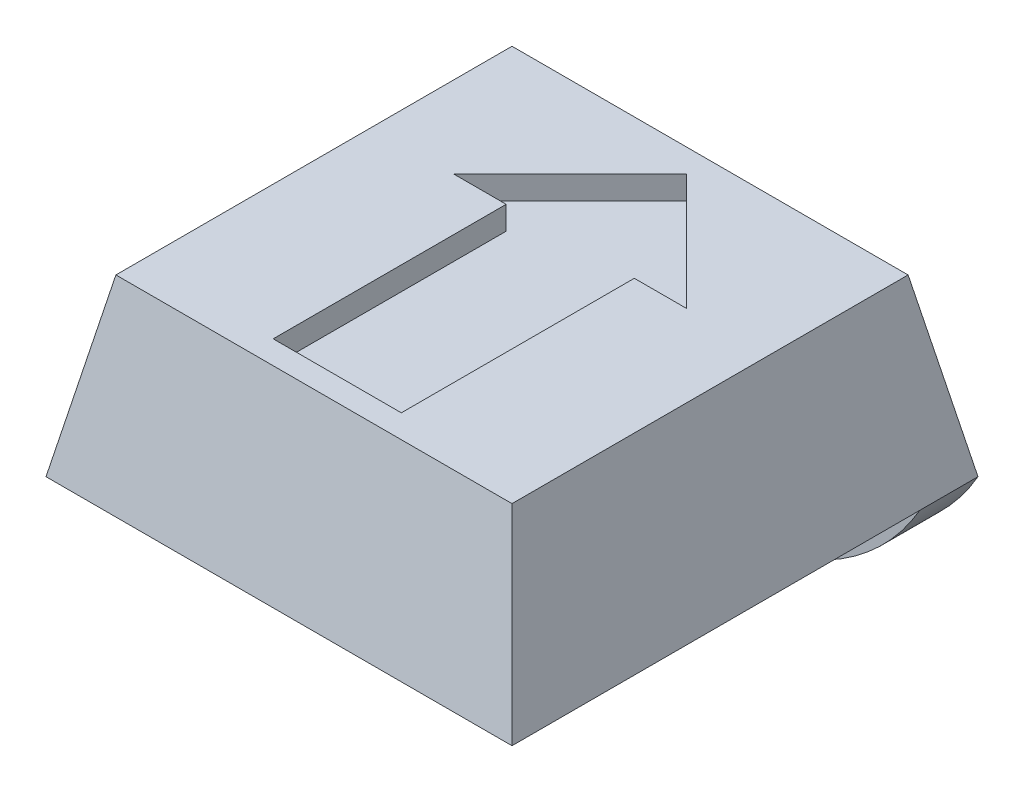
SolidWorks part; units mm, degrees
ref_plane "Front Plane" through (0, 0, 0) normal (0, 0, 1) x (1, 0, 0)
ref_plane "Top Plane" through (0, 0, 0) normal (0, 1, 0) x (1, 0, 0)
ref_plane "Right Plane" through (0, 0, 0) normal (1, 0, 0) x (0, 0, -1)
sketch "Sketch1" plane through (0, 0, 0) normal (0, 1, 0) x (1, 0, 0)
  line L1 (0, 0) -> (8, 0)
  line L2 (0, 0) -> (0, 8)
  line L3 (0, 8) -> (8, 8)
  line L4 (8, 0) -> (8, 8)
  dimension "D1" = 8
  dimension "D2" = 8
extrude "Boss-Extrude1" add sketch "Sketch1" along normal blind 3
sketch "Sketch2" plane through (0, 0, 0) normal (0, 0, 1) x (1, 0, 0)
  line L0 (0, 0) -> (0.6, 3)
  line L1 (0, 3) -> (8, 3) construction
  line L2 (0.6, 3) -> (0, 3)
  line L3 (0, 3) -> (0, 0)
  line L4 (8, 0) -> (7.4, 3)
  line L5 (7.4, 3) -> (8, 3)
  line L6 (8, 3) -> (8, 0)
  dimension "D1" = 0.6
  dimension "D2" = 0.6
extrude "Cut-Extrude1" cut sketch "Sketch2" against normal through all both and the other way through all
sketch "Sketch3" plane through (0, 0, 0) normal (1, 0, 0) x (0, 0, -1)
  line L0 (0, 0) -> (0.6, 3)
  line L1 (8, 3) -> (0, 3) construction
  line L2 (0.6, 3) -> (0, 3)
  line L3 (0, 3) -> (0, 0)
  line L4 (8, 3) -> (7.4, 3)
  line L5 (7.4, 3) -> (8, 0)
  line L6 (8, 3) -> (8, 0)
  dimension "D1" = 0.6
  dimension "D2" = 0.6
extrude "Cut-Extrude2" cut sketch "Sketch3" along normal blind 11
sketch "Sketch4" plane through (0, 0, 0) normal (0, -1, 0) x (1, 0, 0)
  line L0 (8, 0) -> (8, -8) construction
  line L3 (0, 0) -> (8, 0) construction
  circle A0 centre (4, -3.75) radius 1.8
  dimension "D1" = 3.6
  dimension "D2" = 4
  dimension "D3" = 3.75
extrude "Cut-Extrude3" cut sketch "Sketch4" against normal blind 0.8
sketch "Sketch5" plane through (0, 0, 0) normal (0, -1, 0) x (1, 0, 0)
  line L0 (8, 0) -> (8, -8) construction
  line L1 (0, -8) -> (8, -8)
  line L2 (0, -8) -> (0, -7)
  line L3 (0, -7) -> (8, -7)
  line L4 (8, -8) -> (8, -7)
  dimension "D1" = 1
extrude "Boss-Extrude2" add sketch "Sketch5" along normal blind 2
fillet "Fillet1" radius 4 2 edges at (8, -2, -7.5) (0, -2, -7.5)
sketch "Sketch6" plane through (0, 3, 0) normal (0, 1, 0) x (1, 0, 0)
  line L0 (2.9, 5) -> (2, 5)
  line L1 (2.9, 5) -> (5.1, 5)
  line L2 (2.9, 5) -> (2.9, 1)
  line L3 (2.9, 1) -> (5.1, 1)
  line L4 (5.1, 5) -> (5.1, 1)
  line L5 (2, 5) -> (4, 7)
  line L6 (4, 7) -> (6, 5)
  line L7 (6, 5) -> (5.1, 5)
  line L8 (0.6, 7.4) -> (0.6, 0.6) construction
  line L9 (7.4, 7.4) -> (7.4, 0.6) construction
  line L10 (7.4, 0.6) -> (0.6, 0.6) construction
  line L11 (7.4, 7.4) -> (0.6, 7.4) construction
  point P15 (4, 7.4)
  dimension "D1" = 2.3
  dimension "D2" = 2.3
  dimension "D3" = 0.4
  dimension "D4" = 0.4
  dimension "D5" = 1.4
  dimension "D6" = 1.4
  dimension "D7" = 0
  dimension "D8" = 4
extrude "Cut-Extrude4" cut sketch "Sketch6" against normal blind 0.4 contours L4 L1 L2 L3 | L7 L6 L5 L0 L1 region at (4, 3, -5.6667) region at (4, 3, -3)
